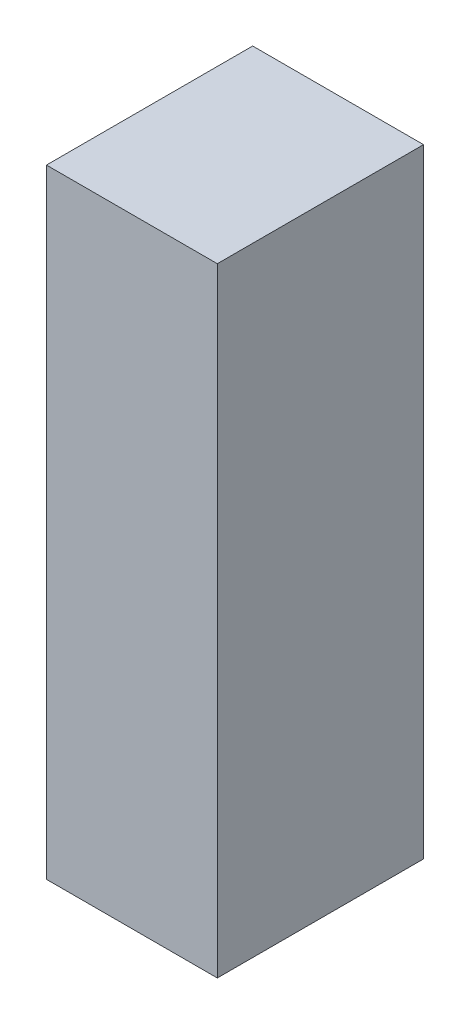
SolidWorks part; units mm, degrees
ref_plane "Front Plane" through (0, 0, 0) normal (0, 0, 1) x (1, 0, 0)
ref_plane "Top Plane" through (0, 0, 0) normal (0, 1, 0) x (1, 0, 0)
ref_plane "Right Plane" through (0, 0, 0) normal (1, 0, 0) x (0, 0, -1)
sketch "Sketch1" plane through (0, 0, 0) normal (0, 1, 0) x (1, 0, 0)
  line L1 (0, 0) -> (29, 0)
  line L2 (0, 0) -> (0, 35)
  line L3 (0, 35) -> (29, 35)
  line L4 (29, 0) -> (29, 35)
  dimension "D1" = 29
  dimension "D2" = 35
extrude "Boss-Extrude1" add sketch "Sketch1" along normal blind 105
